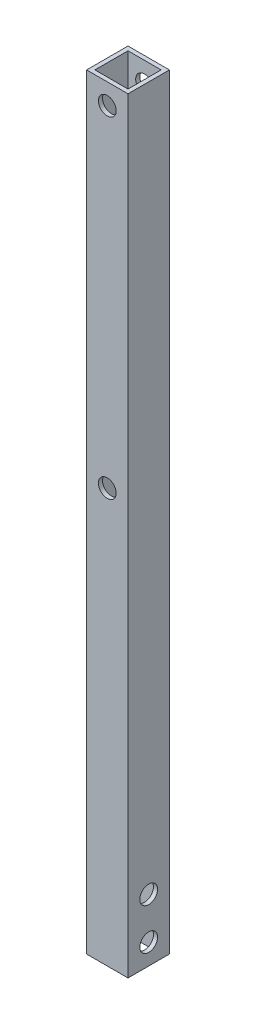
SolidWorks part; units mm, degrees
material "5052-H34"
ref_plane "正面" through (0, 0, 0) normal (0, 0, 1) x (1, 0, 0)
ref_plane "平面" through (0, 0, 0) normal (0, 1, 0) x (1, 0, 0)
ref_plane "右側面" through (0, 0, 0) normal (1, 0, 0) x (0, 0, -1)
sketch "ｽｹｯﾁ1" plane through (0, 0, 0) normal (0, 1, 0) x (1, 0, 0)
  line L1 (-5, 5) -> (5, 5)
  line L2 (-5, 5) -> (-5, -5)
  line L3 (-5, -5) -> (5, -5)
  line L4 (5, 5) -> (5, -5)
  line L5 (-5, 5) -> (5, -5) construction
  line L6 (-5, -5) -> (5, 5) construction
  point P0 (0, 0)
  dimension "D1" = 10
  dimension "D2" = 10
extrude "押し出し-薄板1" add sketch "ｽｹｯﾁ1" along normal blind 185 thin thin type one direction reverse wall 1
sketch "ｽｹｯﾁ2" plane through (5, 0, 0) normal (1, 0, 0) x (0, 0, -1)
  line L0 (0, 15) -> (0, 0) construction
  line L3 (-5, 0) -> (5, 0) construction
  circle A3 centre (0, 5) radius 2.15
  circle A4 centre (0, 15) radius 2.15
  dimension "D5" = 4.3
  dimension "D6" = 5
  dimension "D7" = 10
extrude "ｶｯﾄ - 押し出し1" cut sketch "ｽｹｯﾁ2" against normal through all
sketch "ｽｹｯﾁ3" plane through (0, 0, 5) normal (0, 0, 1) x (1, 0, 0)
  line L0 (0, 0) -> (0, 185) construction
  line L2 (-5, 185) -> (5, 185) construction
  line L3 (0, 140) -> (5, 140) construction
  line L4 (5, 185) -> (5, 0) construction
  circle A2 centre (0, 170) radius 2.15 construction
  circle A3 centre (0, 110) radius 2.15 construction
  circle A4 centre (0, 180) radius 2.15
  circle A5 centre (0, 100) radius 2.15
  dimension "D2" = 4.3
  dimension "D7" = 4.3
  dimension "D1" = 140
  dimension "D5" = 60
  dimension "D6" = 30
  dimension "D8" = 80
extrude "ｶｯﾄ - 押し出し2" cut sketch "ｽｹｯﾁ3" against normal through all
